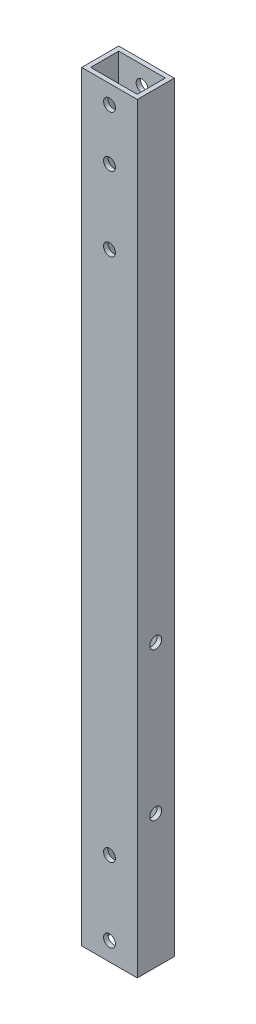
SolidWorks part; units mm, degrees
ref_plane "正面" through (0, 0, 0) normal (0, 0, 1) x (1, 0, 0)
ref_plane "平面" through (0, 0, 0) normal (0, 1, 0) x (1, 0, 0)
ref_plane "右側面" through (0, 0, 0) normal (1, 0, 0) x (0, 0, -1)
sketch "ｽｹｯﾁ1" plane through (0, 0, 0) normal (0, 1, 0) x (1, 0, 0)
  line L0 (-6.3, 3.8) -> (6.3, 3.8)
  line L1 (-7.5, 5) -> (7.5, 5)
  line L2 (-7.5, 5) -> (-7.5, -5)
  line L3 (-7.5, -5) -> (7.5, -5)
  line L4 (7.5, 5) -> (7.5, -5)
  line L5 (-7.5, 5) -> (7.5, -5) construction
  line L6 (-7.5, -5) -> (7.5, 5) construction
  line L7 (6.3, 3.8) -> (6.3, -3.8)
  line L8 (-6.3, -3.8) -> (6.3, -3.8)
  line L9 (-6.3, 3.8) -> (-6.3, -3.8)
  point P0 (0, 0)
  dimension "D1" = 15
  dimension "D2" = 10
  dimension "D3" = 1.2
extrude "ﾎﾞｽ - 押し出し1" add sketch "ｽｹｯﾁ1" along normal mid plane 220
sketch "ｽｹｯﾁ2" plane through (0, 0, -5) normal (0, 0, -1) x (-1, 0, 0)
  line L0 (0, -110) -> (0, -85) construction
  line L1 (-7.5, -110) -> (7.5, -110) construction
  circle A0 centre (0, -85) radius 1.6
  circle A1 centre (0, -105) radius 1.6
  dimension "D2" = 3.2
  dimension "D3" = 3.2
  dimension "D1" = 25
  dimension "D4" = 20
extrude "ｶｯﾄ - 押し出し1" cut sketch "ｽｹｯﾁ2" against normal blind 100
sketch "ｽｹｯﾁ3" plane through (-7.5, 0, 0) normal (-1, 0, 0) x (0, 0, 1)
  line L0 (0, -110) -> (0, 0) construction
  line L1 (-5, -110) -> (5, -110) construction
  circle A0 centre (0, -74) radius 1.6
  circle A1 centre (0, -34) radius 1.6
  dimension "D1" = 3.2
  dimension "D2" = 3.2
extrude "ｶｯﾄ - 押し出し2" cut sketch "ｽｹｯﾁ3" against normal blind 15
sketch "ｽｹｯﾁ5" plane through (0, 110, 0) normal (0, 1, 0) x (1, 0, 0)
  line L4 (7.5, -5) -> (7.5, 5)
  line L5 (7.5, 5) -> (-7.5, 5)
  line L6 (-7.5, 5) -> (-7.5, -5)
  line L7 (-7.5, -5) -> (7.5, -5)
  line L8 (7.5, -5) -> (7.5, 5)
  line L9 (7.5, 5) -> (-7.5, 5)
  line L10 (-7.5, 5) -> (-7.5, -5)
  line L11 (-7.5, -5) -> (7.5, -5)
  dimension "D1" = 0
extrude "ｶｯﾄ - 押し出し4" cut sketch "ｽｹｯﾁ5" against normal blind 14.5
sketch "ｽｹｯﾁ6" plane through (0, 0, -5) normal (0, 0, -1) x (-1, 0, 0)
  line L0 (0, 95.5) -> (0, 90.5) construction
  line L1 (-7.5, 95.5) -> (7.5, 95.5) construction
  line L2 (0, 90.5) -> (0, 76.66) construction
  line L3 (0, 76.66) -> (0, 56.66) construction
  circle A0 centre (0, 90.5) radius 1.6
  circle A1 centre (0, 76.66) radius 1.6
  circle A2 centre (0, 56.66) radius 1.6
  dimension "D2" = 3.2
  dimension "D4" = 3.2
  dimension "D6" = 3.2
  dimension "D1" = 5
  dimension "D3" = 13.84
  dimension "D5" = 20
extrude "ｶｯﾄ - 押し出し5" cut sketch "ｽｹｯﾁ6" against normal blind 15
